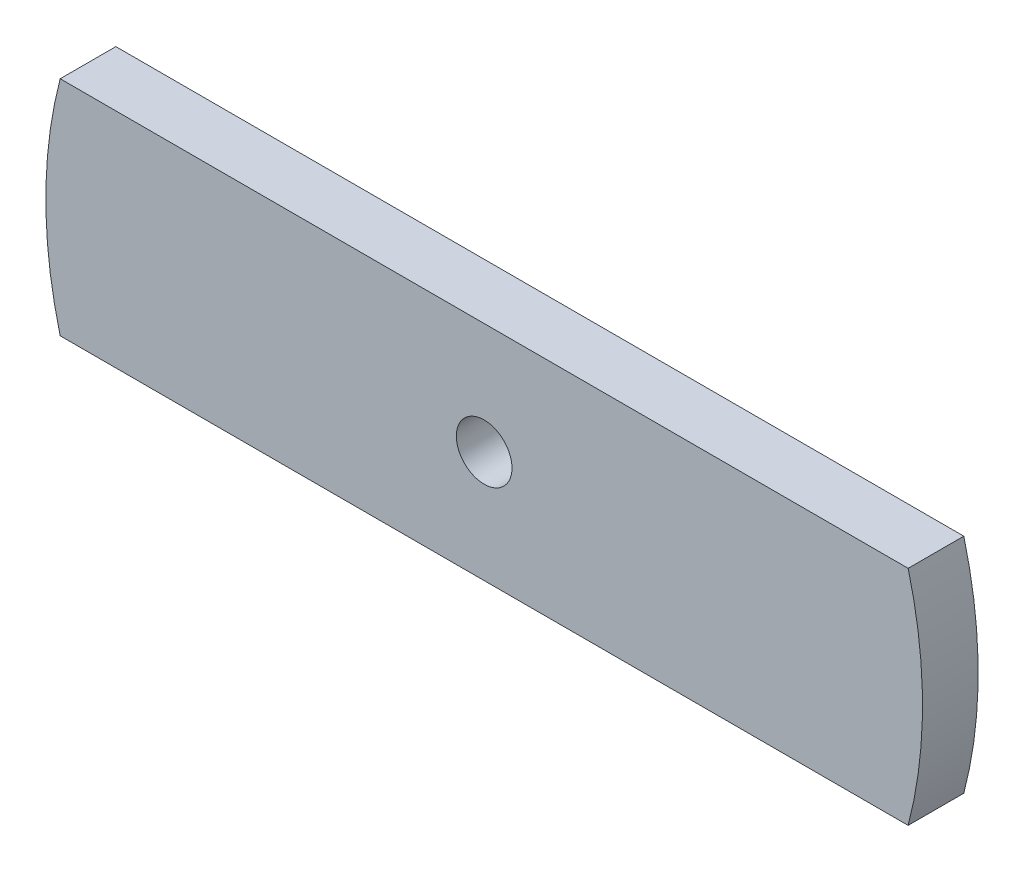
SolidWorks part; units mm, degrees
ref_plane "Front Plane" through (0, 0, 0) normal (0, 0, 1) x (1, 0, 0)
ref_plane "Top Plane" through (0, 0, 0) normal (0, 1, 0) x (1, 0, 0)
ref_plane "Right Plane" through (0, 0, 0) normal (1, 0, 0) x (0, 0, -1)
sketch "Sketch1" plane through (0, 0, 0) normal (0, 0, 1) x (1, 0, 0)
  line L1 (0, 0) -> (100.0125, 0)
  line L2 (0, 0) -> (0, 25.4)
  line L3 (0, 25.4) -> (100.0125, 25.4)
  line L4 (100.0125, 0) -> (100.0125, 25.4)
  dimension "D1" = 25.4
  dimension "D2" = 100.0125
extrude "Extrude1" add sketch "Sketch1" along normal blind 6.35
sketch "Sketch2" plane through (0, 0, 6.35) normal (0, 0, 1) x (1, 0, 0)
  line L0 (0, 12.7) -> (100.0125, 12.7) construction
  line L1 (0, 25.4) -> (0, 0) construction
  line L2 (100.0125, 0) -> (100.0125, 25.4) construction
  line L14 (50.0062, 12.7) -> (50.0063, 25.4) construction
  line L15 (-6.35, 25.4) -> (-6.35, 0)
  line L16 (-6.35, 25.4) -> (-6.35, 0)
  line L17 (100.0125, 25.4) -> (0, 25.4) construction
  line L18 (0, 0) -> (100.0125, 0) construction
  line L19 (-6.35, 0) -> (1.6396, 0)
  line L20 (106.3625, 0) -> (98.3729, 0)
  line L21 (1.6396, 25.4) -> (-6.35, 25.4)
  line L23 (106.3625, 25.4) -> (106.3625, 0)
  line L24 (98.3729, 25.4) -> (106.3625, 25.4)
  arc A0 (1.6396, 25.4) -> (1.6396, 0) centre (50.0062, 12.7) ccw
  arc A1 (98.3729, 25.4) -> (98.3729, 0) centre (50.0062, 12.7) cw
  circle A2 centre (50.0062, 12.7) radius 3.175
  dimension "D2" = 6.35
  dimension "D1" = 6.35
extrude "Extrude2" cut sketch "Sketch2" against normal up to next (6.35 mm away)
